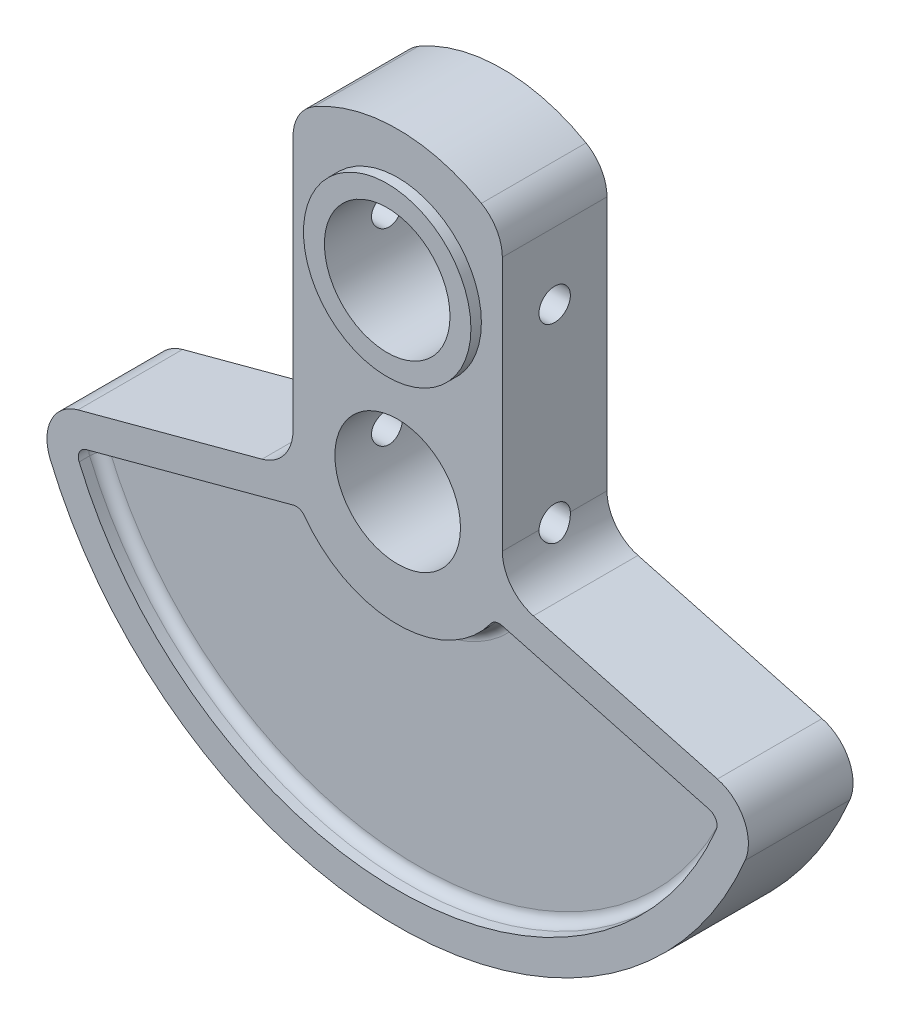
SolidWorks part; units mm, degrees
ref_plane "Front Plane" through (0, 0, 0) normal (0, 0, 1) x (1, 0, 0)
ref_plane "Top Plane" through (0, 0, 0) normal (0, 1, 0) x (1, 0, 0)
ref_plane "Right Plane" through (0, 0, 0) normal (1, 0, 0) x (0, 0, -1)
sketch "Sketch1" plane through (0, 0, 0) normal (0, 0, 1) x (1, 0, 0)
  line L1 (-10, 62.49) -> (-10, 33)
  line L2 (-10, 33) -> (-34.6919, 26.3838)
  line L3 (34.6919, 26.3838) -> (10, 33)
  line L4 (10, 33) -> (10, 62.49)
  line L5 (0, 0) -> (0, 68.8191) construction
  circle A9 centre (0, 36) radius 6
  circle A10 centre (0, 54) radius 6
  arc A11 (10, 62.49) -> (-10, 62.49) centre (0, 50) ccw
  arc A12 (-34.6919, 26.3838) -> (34.6919, 26.3838) centre (0, 36) ccw
  point P2 (0, 0)
  point P4 (0, 0)
  point P7 (0, 11.0053)
  point P11 (0, 0)
  point P12 (0, 0)
  point P13 (0, 0)
  point P14 (0, 0)
  point P15 (0, 0)
  point P16 (0, 0)
  point P17 (0, 0)
  point P18 (0, 66)
  point P20 (-15.0888, 55.3224)
  point P21 (-14.1953, 57.382)
  point P23 (0, 0)
  point P24 (0, 0)
  point P26 (0, 0)
  point P30 (0, 0)
  point P31 (0, 0)
  point P32 (0, 0)
  point P33 (0, 0)
  point P34 (0, 0)
  dimension "D2" = 30
  dimension "D3" = 16
  dimension "D7" = 12
  dimension "D8" = 18
  dimension "D4" = 75
  dimension "D1" = 72
  dimension "D6" = 20
  dimension "D9" = 3
  dimension "D5" = 75
extrude "Boss-Extrude2" add sketch "Sketch1" along normal mid plane 10
fillet "Fillet2" radius 4 6 edges at (-34.6919, 26.3838, 0) (34.6919, 26.3838, 0) (10, 33, 0) (-10, 33, 0) (10, 62.49, 0) (-10, 62.49, 0)
sketch "Sketch2" plane through (0, 0, 5) normal (0, 0, 1) x (1, 0, 0)
  line L4 (-9.2763, 30.0881) -> (-29.7715, 24.5964)
  line L5 (-9.9612, 29.9046) -> (-29.7715, 24.5964)
  line L8 (29.7715, 24.5964) -> (9.9612, 29.9046)
  arc A0 (9.9612, 29.9046) -> (8.8939, 29.5271) centre (9.7024, 28.9386) ccw
  arc A1 (-8.8939, 29.5271) -> (-9.9612, 29.9046) centre (-9.7024, 28.9386) ccw
  arc A2 (-29.7715, 24.5964) -> (-30.4349, 23.244) centre (-29.5126, 23.6305) ccw
  arc A3 (-29.7715, 24.5964) -> (-30.4349, 23.244) centre (-29.5126, 23.6305) ccw
  arc A6 (-8.8939, 29.5271) -> (8.8939, 29.5271) centre (0, 36) ccw
  arc A8 (30.4349, 23.244) -> (29.7715, 24.5964) centre (29.5126, 23.6305) ccw
  arc A9 (-30.4349, 23.244) -> (30.4349, 23.244) centre (0, 36) ccw
  arc A10 (30.4349, 23.244) -> (29.7715, 24.5964) centre (29.5126, 23.6305) ccw
  arc A11 (-30.4349, 23.244) -> (30.4349, 23.244) centre (0, 36) ccw
  point P0 (0, 0)
  dimension "D4" = 22
  dimension "D3" = 1
  dimension "D1" = 3
  dimension "D2" = 3
extrude "Cut-Extrude1" cut sketch "Sketch2" against normal blind 2
mirror "Mirror1" about plane through (0, 0, 0) normal (0, 0, 1) of "Cut-Extrude1"
sketch "Sketch3" plane through (0, 0, 5) normal (0, 0, 1) x (1, 0, 0)
  circle A0 centre (0, 54) radius 8
  circle A1 centre (0, 54) radius 6 construction
  circle A2 centre (0, 54) radius 6
  dimension "D1" = 16
extrude "Boss-Extrude3" add sketch "Sketch3" along normal blind 1
sketch "Sketch4" plane through (0, 0, -5) normal (0, 0, -1) x (-1, 0, 0)
  circle A0 centre (0, 36) radius 8
  circle A1 centre (0, 36) radius 6 construction
  circle A2 centre (0, 36) radius 6
  dimension "D1" = 16
extrude "Boss-Extrude4" add sketch "Sketch4" along normal blind 1
sketch "Sketch5" plane through (0, 0, 0) normal (1, 0, 0) x (0, 0, -1)
  circle A0 centre (0, 54) radius 1.5
  circle A1 centre (0, 36) radius 1.5
  point P4 (0, 0)
  point P6 (0, 0)
  dimension "D3" = 3
  dimension "D1" = 36
  dimension "D2" = 18
extrude "Cut-Extrude2" cut sketch "Sketch5" against normal through all both and the other way through all
fillet "Fillet3" radius 1 16 edges at (19.8663, 27.2505, 3) (30.4104, 24.0709, 3) (0, 3, 3) (-30.4104, 24.0709, 3) (-19.8663, 27.2505, 3) (-9.369, 29.8814, 3) (0, 25, 3) (9.369, 29.8814, 3) (0, 25, -3) (-9.369, 29.8814, -3) (-19.8663, 27.2505, -3) (-30.4104, 24.0709, -3) (0, 3, -3) (30.4104, 24.0709, -3) (19.8663, 27.2505, -3) (9.369, 29.8814, -3)
